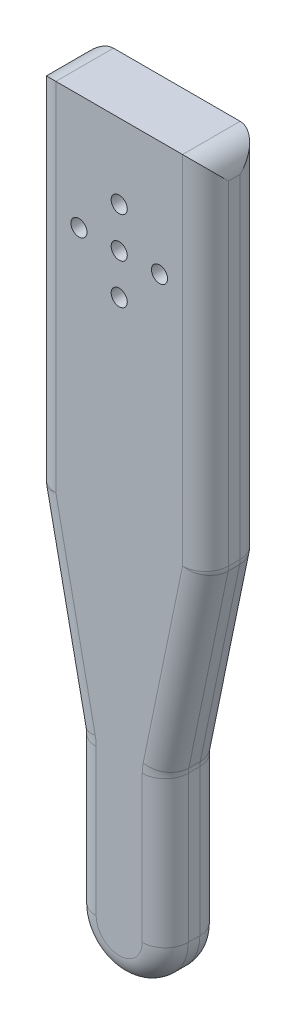
SolidWorks part; units mm, degrees
ref_plane "Front Plane" through (0, 0, 0) normal (0, 0, 1) x (1, 0, 0)
ref_plane "Top Plane" through (0, 0, 0) normal (0, 1, 0) x (1, 0, 0)
ref_plane "Right Plane" through (0, 0, 0) normal (1, 0, 0) x (0, 0, -1)
sketch "Sketch2" plane through (0, 0, 0) normal (0, 0, 1) x (1, 0, 0)
  line L1 (-29.8024, 62.3024) -> (0.1976, 62.3024)
  line L2 (-29.8024, 62.3024) -> (-29.8024, -67.6976)
  line L3 (-29.8024, -67.6976) -> (0.1976, -67.6976)
  line L4 (0.1976, 62.3024) -> (0.1976, -67.6976)
  dimension "D1" = 130
extrude "Boss-Extrude1" add sketch "Sketch2" along normal blind 10
sketch "Sketch3" plane through (0, 0, 10) normal (0, 0, 1) x (1, 0, 0)
  line L0 (-14.8024, 62.3024) -> (-14.8024, 42.3024) construction
  line L1 (0.1976, 62.3024) -> (-29.8024, 62.3024) construction
  line L4 (-29.8024, -67.6976) -> (-21.8024, -67.6976)
  line L5 (-29.8024, -67.6976) -> (-29.8024, 0)
  line L6 (-29.8024, 0) -> (-21.8024, 0)
  line L7 (-21.8024, -67.6976) -> (-21.8024, 0)
  line L9 (0, 0) -> (-7.8024, 0)
  line L10 (0, 0) -> (0, -67.6976)
  line L11 (0, -67.6976) -> (-7.8024, -67.6976)
  line L12 (-7.8024, 0) -> (-7.8024, -67.6976)
  line L13 (-29.8024, -67.6976) -> (0.1976, -67.6976) construction
  circle A0 centre (-14.8024, 42.3024) radius 7 construction
  circle A1 centre (-21.8024, 42.3024) radius 1.4
  circle A2 centre (-14.8024, 49.3024) radius 1.4
  circle A3 centre (-7.8024, 42.3024) radius 1.4
  circle A4 centre (-14.8024, 35.3024) radius 1.4
  circle A5 centre (-14.8024, 42.3024) radius 1.4
  point P5 (-21.8024, 42.3024)
  point P7 (-14.8024, 49.3024)
  point P9 (-7.8024, 42.3024)
  point P11 (-14.8024, 35.3024)
sketch "Sketch6" plane through (0, 0, 10) normal (0, 0, 1) x (1, 0, 0)
  line L1 (-29.8024, -67.6976) -> (-22.8024, -67.6976)
  line L2 (-29.8024, -67.6976) -> (-29.8024, 0)
  line L4 (-22.8024, -67.6976) -> (-22.8024, -33.8488)
  line L11 (0.1976, -67.6976) -> (-6.8024, -67.6976)
  line L12 (0.1976, -67.6976) -> (0.1976, 0)
  line L14 (-6.8024, -67.6976) -> (-6.8024, -33.8488)
  line L15 (-29.8024, 0) -> (-22.8024, -33.8488)
  line L16 (-6.8024, -33.8488) -> (0.1976, 0)
  dimension "D1" = 7
extrude "Cut-Extrude3" cut sketch "Sketch6" against normal through all contours L14 L16 L12 L11 | L4 L15 L2 L1
fillet "Fillet3" 2 edges at (-22.8024, -67.6976, 5) (-6.8024, -67.6976, 5) type full round first side face at (-22.8024, -50.7732, 5) second side face at (-6.8024, -50.7732, 5) middle face at (-14.8024, -67.6976, 5)
fillet "Fillet4" radius 4 20 edges at (-14.8024, -67.6976, 0) (-14.8024, -67.6976, 10) (-6.8024, -46.7732, 0) (-6.8024, -46.7732, 10) (-22.8024, -46.7732, 0) (-22.8024, -46.7732, 10) (0.1976, 31.1512, 10) (0.1976, 62.3024, 5) (0.1976, 31.1512, 0) (0.1976, 0, 5) (-3.3024, -16.9244, 0) (-6.8024, -33.8488, 5) (-3.3024, -16.9244, 10) (-22.8024, -33.8488, 5) (-26.3024, -16.9244, 0) (-26.3024, -16.9244, 10) (-29.8024, 31.1512, 0) (-29.8024, 62.3024, 5) (-29.8024, 31.1512, 10) (-29.8024, 0, 5)
extrude "Cut-Extrude4" cut sketch "Sketch3" against normal through all contours A1 | A4 | A3 | A2 | A5
